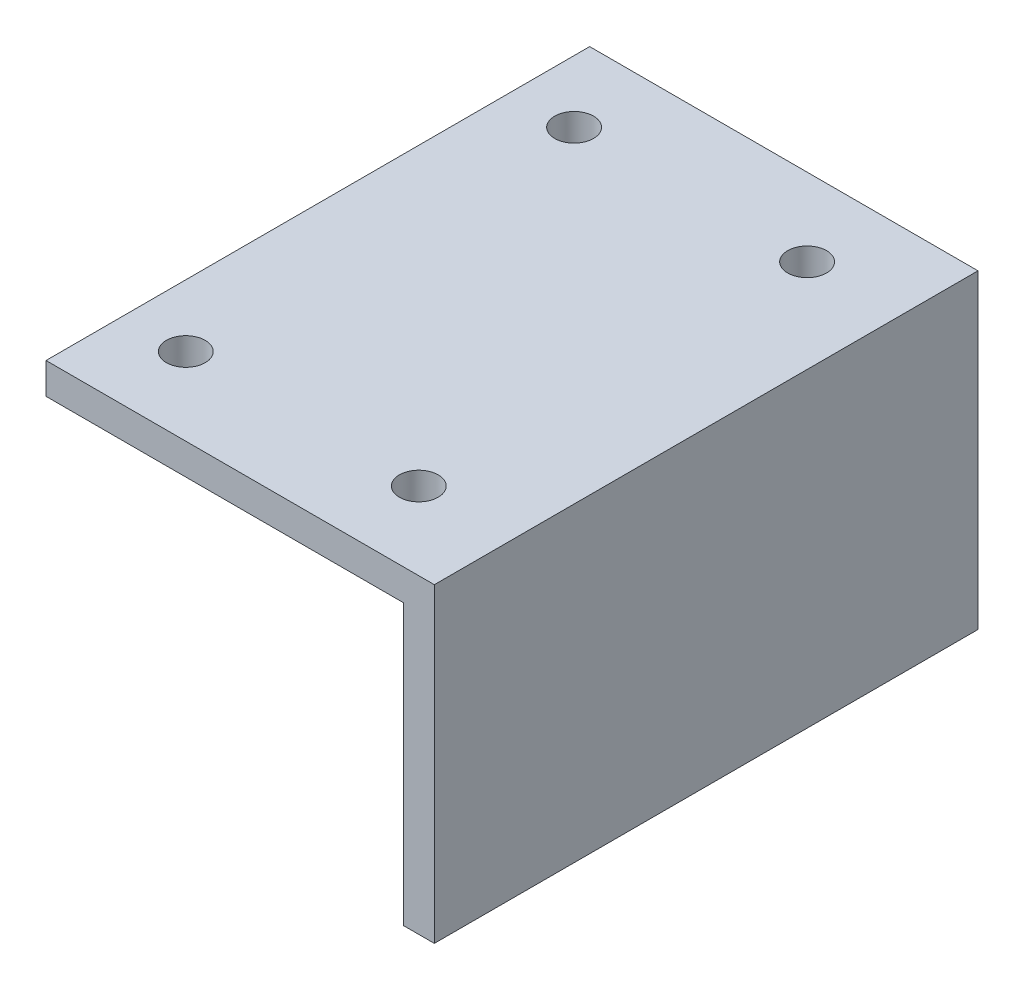
SolidWorks part; units mm, degrees
ref_plane "Alzado" through (0, 0, 0) normal (0, 0, 1) x (1, 0, 0)
ref_plane "Planta" through (0, 0, 0) normal (0, 1, 0) x (1, 0, 0)
ref_plane "Vista lateral" through (0, 0, 0) normal (1, 0, 0) x (0, 0, -1)
sketch "Croquis2" plane through (0, 0, 0) normal (0, 0, 1) x (1, 0, 0)
  line L0 (0, 0) -> (-50, 0)
  line L1 (0, 0) -> (0, -50)
  line L2 (-4, -4) -> (-4, -50)
  line L3 (-4, -4) -> (-50, -4)
  line L4 (-50, 0) -> (-50, -4)
  line L5 (-4, -50) -> (0, -50)
  dimension "D1" = 50
  dimension "D2" = 4
extrude "Saliente-Extruir1" add sketch "Croquis2" along normal blind 35 and the other way blind 35
sketch "Croquis3" plane through (0, -4, 0) normal (0, -1, 0) x (1, 0, 0)
  line L0 (-4, 0) -> (-50, 0) construction
  line L1 (-42, 25) -> (-12, 25) construction
  line L2 (-42, 25) -> (-42, -25) construction
  line L3 (-42, -25) -> (-12, -25) construction
  line L4 (-12, 25) -> (-12, -25) construction
  line L5 (-42, 25) -> (-12, -25) construction
  line L6 (-42, -25) -> (-12, 25) construction
  line L7 (-4, 35) -> (-4, -35) construction
  line L8 (-50, 35) -> (-50, -35) construction
  circle A0 centre (-12, 25) radius 2.5
  circle A1 centre (-12, -25) radius 2.5
  circle A2 centre (-42, 25) radius 2.5
  circle A3 centre (-42, -25) radius 2.5
  point P0 (-27, 0)
  dimension "D3" = 5
  dimension "D1" = 30
  dimension "D2" = 50
extrude "Cortar-Extruir1" cut sketch "Croquis3" against normal up to surface (4 mm away) up to face at (-25, 0, 0)
sketch "Croquis4" plane through (-4, 0, 0) normal (-1, 0, 0) x (0, 0, 1)
  line L0 (35, -40) -> (-35, -40)
  line L1 (35, -4) -> (35, -50) construction
  line L2 (-35, -4) -> (-35, -50) construction
  line L3 (-35, -40) -> (-35, -50)
  line L4 (-35, -50) -> (35, -50)
  line L5 (35, -50) -> (35, -40)
  dimension "D1" = 10
extrude "Cortar-Extruir2" cut sketch "Croquis4" against normal blind 10
